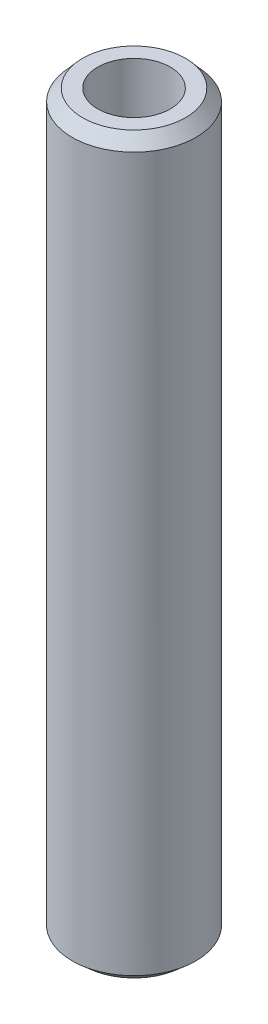
SolidWorks part; units mm, degrees
ref_plane "Front Plane" through (0, 0, 0) normal (0, 0, 1) x (1, 0, 0)
ref_plane "Top Plane" through (0, 0, 0) normal (0, 1, 0) x (1, 0, 0)
ref_plane "Right Plane" through (0, 0, 0) normal (1, 0, 0) x (0, 0, -1)
sketch "Sketch1" plane through (0, 0, 0) normal (0, 1, 0) x (1, 0, 0)
  circle A0 centre (0, 0) radius 27.5
  dimension "SHAFT_OD" = 55
extrude "Boss-Extrude1" add sketch "Sketch1" along normal blind 326.8542
sketch "Sketch2" plane through (0, 0, 0) normal (0, 1, 0) x (1, 0, 0)
  circle A0 centre (0, 0) radius 16.1286
  dimension "BORE_D" = 32.2573
extrude "Cut-Extrude1" cut sketch "Sketch2" along normal through all
chamfer "Chamfer1" distance 5.2712 angle 41.199 2 edges at (0, 326.8542, 27.5) (0, 0, 27.5) first distance on face at (0, 326.8542, 27.5) first distance on face at (0, 0, 16.1286)
